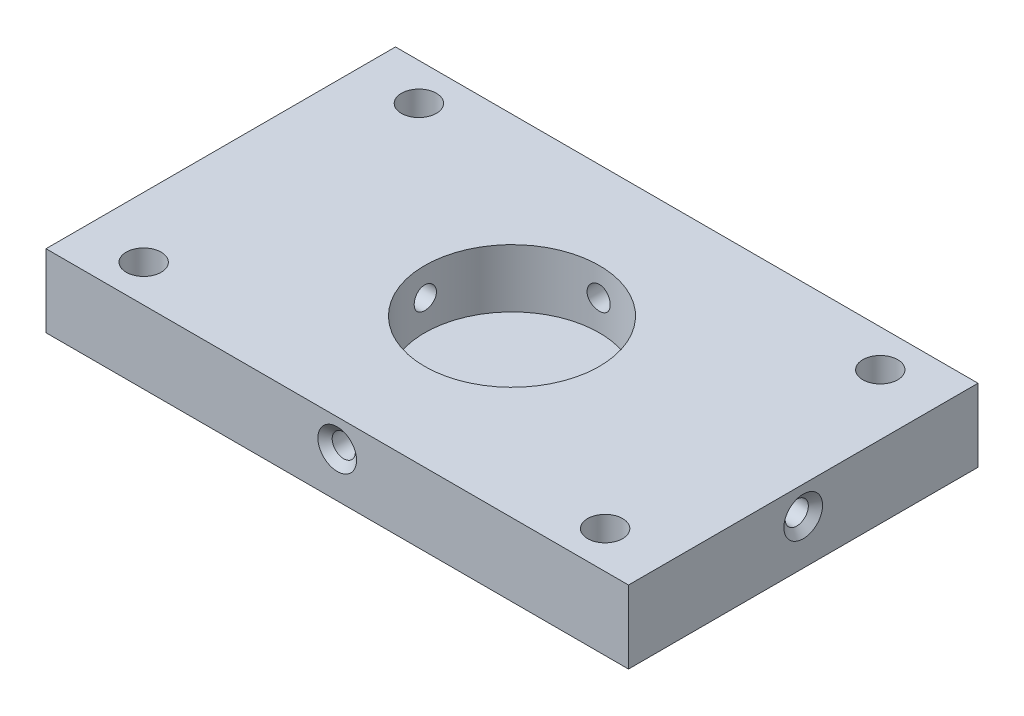
SolidWorks part; units mm, degrees
ref_plane "Front Plane" through (0, 0, 0) normal (0, 0, 1) x (1, 0, 0)
ref_plane "Top Plane" through (0, 0, 0) normal (0, 1, 0) x (1, 0, 0)
ref_plane "Right Plane" through (0, 0, 0) normal (1, 0, 0) x (0, 0, -1)
sketch "Sketch1" plane through (0, 0, 0) normal (0, 1, 0) x (1, 0, 0)
  line L1 (-63.5, -38.1) -> (63.5, -38.1)
  line L2 (-63.5, -38.1) -> (-63.5, 38.1)
  line L3 (-63.5, 38.1) -> (63.5, 38.1)
  line L4 (63.5, -38.1) -> (63.5, 38.1)
  line L5 (-63.5, -38.1) -> (63.5, 38.1) construction
  line L6 (-63.5, 38.1) -> (63.5, -38.1) construction
  point P0 (0, 0)
  dimension "D1" = 127
  dimension "D2" = 76.2
extrude "Boss-Extrude1" add sketch "Sketch1" along normal blind 15.875
sketch "Sketch2" plane through (0, 15.875, 0) normal (0, 1, 0) x (1, 0, 0)
  circle A0 centre (0, 0) radius 19.05
  dimension "D1" = 38.1
extrude "Cut-Extrude1" cut sketch "Sketch2" against normal blind 12.7
hole_wizard "#8 (0.199) Diameter Hole1" positions "Sketch3" profile "Sketch4" hole size "#8" standard "ANSI Inch" end condition up to next
sketch "Sketch3" plane through (0, 0, -38.1) normal (0, 0, -1) x (-1, 0, 0)
  line L0 (-63.5, 0) -> (63.5, 0) construction
  point P0 (0, 9.779)
  dimension "D1" = 9.779
sketch "Sketch4" plane through (0, 9.779, -38.1) normal (1, 0, 0) x (0, 1, 0)
  line L0 (0, 0) -> (0, 19.05)
  line L1 (0, 19.05) -> (2.5273, 19.05)
  line L2 (2.5273, 19.05) -> (2.5273, 1.4173)
  line L3 (2.5273, 1.4173) -> (4.2164, 0)
  line L5 (4.2164, 0) -> (0, 0)
  line L6 (-2.5273, 1.4173) -> (-4.2164, 0) construction
  line L11 (0, -6.35) -> (0, 107.95) construction
  dimension "Thru Hole Dia." = 5.0546
  dimension "Thru Hole Depth" = 19.05
  dimension "Near C'Sink Dia." = 8.4328
  dimension "Near C'Sink Angle" = 100
hole_wizard "#11 (0.191) Diameter Hole1" positions "Sketch5" profile "Sketch6" hole size "#11" standard "ANSI Inch" end condition up to next
sketch "Sketch5" plane through (-63.5, 0, 0) normal (-1, 0, 0) x (0, 0, 1)
  line L0 (-38.1, 0) -> (38.1, 0) construction
  point P0 (0, 9.779)
  dimension "D1" = 9.779
sketch "Sketch6" plane through (-63.5, 9.779, 0) normal (0, 1, 0) x (0, 0, 1)
  line L0 (0, 0) -> (0, 44.45)
  line L1 (0, 44.45) -> (2.4257, 44.45)
  line L2 (2.4257, 44.45) -> (2.4257, 0.5328)
  line L3 (2.4257, 0.5328) -> (3.0607, 0)
  line L5 (3.0607, 0) -> (0, 0)
  line L6 (-2.4257, 0.5328) -> (-3.0607, 0) construction
  line L11 (0, -6.35) -> (0, 107.95) construction
  dimension "Thru Hole Dia." = 4.8514
  dimension "Thru Hole Depth" = 44.45
  dimension "Near C'Sink Dia." = 6.1214
  dimension "Near C'Sink Angle" = 100
hole_wizard "#8 (0.199) Diameter Hole3" positions "Sketch7" profile "Sketch8" hole size "#8" standard "ANSI Inch" end condition up to next
sketch "Sketch7" plane through (0, 0, 38.1) normal (0, 0, 1) x (1, 0, 0)
  line L0 (-63.5, 0) -> (63.5, 0) construction
  point P0 (0, 9.779)
  dimension "D1" = 9.779
sketch "Sketch8" plane through (0, 9.779, 38.1) normal (1, 0, 0) x (0, -1, 0)
  line L0 (0, 0) -> (0, 19.05)
  line L1 (0, 19.05) -> (2.5273, 19.05)
  line L2 (2.5273, 19.05) -> (2.5273, 1.4173)
  line L3 (2.5273, 1.4173) -> (4.2164, 0)
  line L5 (4.2164, 0) -> (0, 0)
  line L6 (-2.5273, 1.4173) -> (-4.2164, 0) construction
  line L11 (0, -6.35) -> (0, 107.95) construction
  dimension "Thru Hole Dia." = 5.0546
  dimension "Thru Hole Depth" = 19.05
  dimension "Near C'Sink Dia." = 8.4328
  dimension "Near C'Sink Angle" = 100
hole_wizard "#8 (0.199) Diameter Hole4" positions "Sketch9" profile "Sketch10" hole size "#8" standard "ANSI Inch" end condition up to next
sketch "Sketch9" plane through (63.5, 0, 0) normal (1, 0, 0) x (0, 0, -1)
  line L0 (-38.1, 0) -> (38.1, 0) construction
  point P0 (0, 9.779)
  dimension "D1" = 9.779
sketch "Sketch10" plane through (63.5, 9.779, 0) normal (0, 1, 0) x (0, 0, -1)
  line L0 (0, 0) -> (0, 44.45)
  line L1 (0, 44.45) -> (2.5273, 44.45)
  line L2 (2.5273, 44.45) -> (2.5273, 1.4173)
  line L3 (2.5273, 1.4173) -> (4.2164, 0)
  line L5 (4.2164, 0) -> (0, 0)
  line L6 (-2.5273, 1.4173) -> (-4.2164, 0) construction
  line L11 (0, -6.35) -> (0, 107.95) construction
  dimension "Thru Hole Dia." = 5.0546
  dimension "Thru Hole Depth" = 44.45
  dimension "Near C'Sink Dia." = 8.4328
  dimension "Near C'Sink Angle" = 100
sketch "Sketch11" plane through (0, 0, 0) normal (0, -1, 0) x (-1, 0, 0)
  circle A0 centre (50.3, 30) radius 3.81
  circle A1 centre (50.3, -30) radius 3.81
  circle A2 centre (-50.3, -30) radius 3.81
  circle A3 centre (-50.3, 30) radius 3.81
  point P10 (52.9453, 30)
  point P11 (50.3, 30)
  point P13 (-29.5971, 30)
  point P14 (-50.3, 30)
  point P16 (-50.3, -30)
  point P18 (50.3, -30)
  dimension "D1" = 7.62
  dimension "D2" = 7.62
  dimension "D3" = 7.62
  dimension "D4" = 7.62
extrude "Cut-Extrude2" cut sketch "Sketch11" against normal through all
